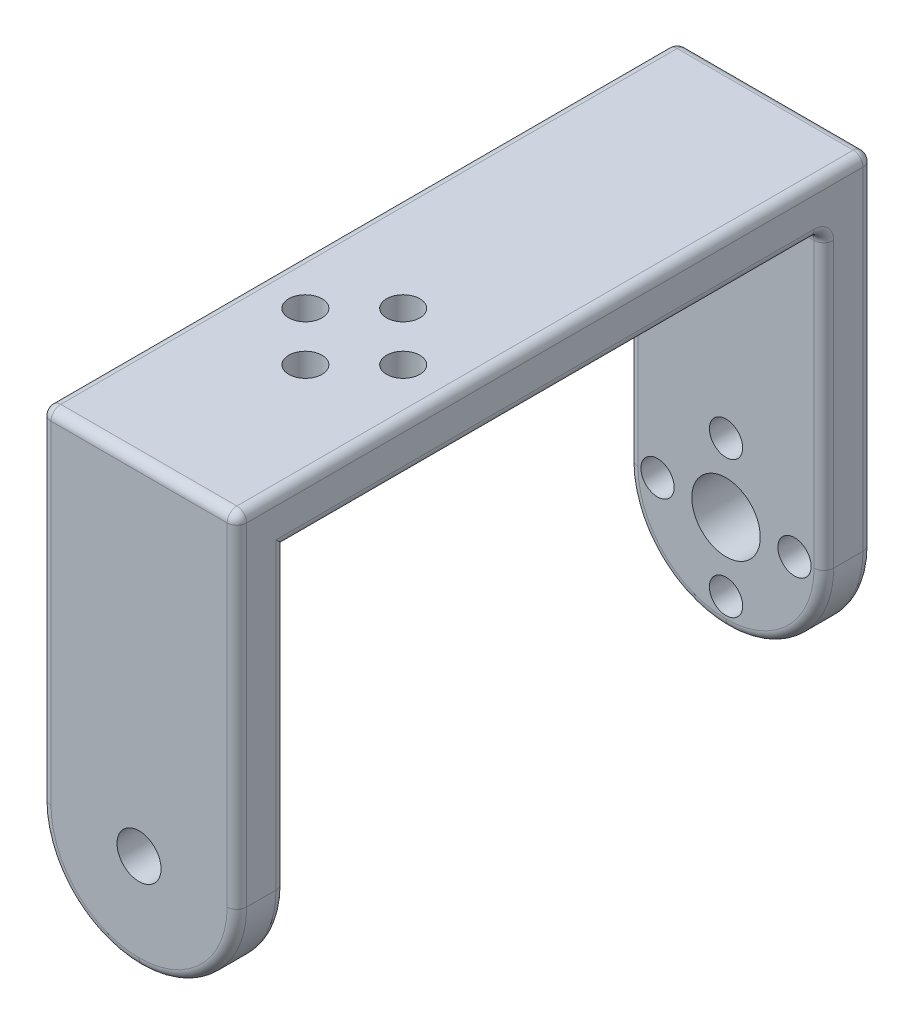
SolidWorks part; units mm, degrees
ref_plane "前视基准面" through (0, 0, 0) normal (0, 0, 1) x (1, 0, 0)
ref_plane "上视基准面" through (0, 0, 0) normal (0, 1, 0) x (1, 0, 0)
ref_plane "右视基准面" through (0, 0, 0) normal (1, 0, 0) x (0, 0, -1)
other "Configuration Table"
sketch "草图1" plane through (0, 0, 0) normal (1, 0, 0) x (0, 0, -1)
  line L0 (0, 0) -> (0, 40)
  line L1 (0, 40) -> (55, 40)
  line L2 (55, 40) -> (55, 0)
  line L3 (55, 0) -> (60, 0)
  line L4 (60, 0) -> (60, 45)
  line L5 (60, 45) -> (-5, 45)
  line L6 (-5, 45) -> (-5, 0)
  line L7 (-5, 0) -> (0, 0)
  dimension "D1" = 5
  dimension "D2" = 5
  dimension "D3" = 5
  dimension "D4" = 55
  dimension "D5" = 40
extrude "凸台-拉伸1" add sketch "草图1" along normal blind 20
fillet "圆角1" radius 10 4 edges at (0, 0, -57.5) (20, 0, -57.5) (0, 0, 2.5) (20, 0, 2.5)
hole_wizard "M3 间隙孔1" positions "草图2" profile "草图3" hole size "M3" standard "GB"
sketch "草图2" plane through (0, 0, -55) normal (0, 0, 1) x (1, 0, 0)
  circle A0 centre (10, 10) radius 7
  point P5 (10, 17)
  point P7 (3, 10)
  point P9 (17, 10)
  point P11 (10, 3)
  dimension "D1" = 14
sketch "草图3" plane through (10, 3, -55) normal (1, 0, 0) x (0, -1, 0)
  line L0 (0, 0) -> (0, 21.0215)
  line L1 (0, 21.0215) -> (1.7, 20)
  line L2 (1.7, 20) -> (1.7, 0)
  line L5 (1.7, 0) -> (0, 0)
  line L10 (0, 21.0215) -> (-1.7, 20) construction
  line L11 (0, -6.35) -> (0, 107.95) construction
  dimension "孔直径" = 3.4
  dimension "孔深度" = 20
  dimension "导头角度" = 118
hole_wizard "M4 间隙孔1" positions "草图4" profile "草图5" hole size "M4" standard "GB"
sketch "草图4" plane through (0, 0, 0) normal (0, 0, -1) x (-1, 0, 0)
  point P0 (-10, 10)
sketch "草图5" plane through (10, 10, 0) normal (1, 0, 0) x (0, 1, 0)
  line L0 (0, 0) -> (0, 21.3519)
  line L1 (0, 21.3519) -> (2.25, 20)
  line L2 (2.25, 20) -> (2.25, 0)
  line L5 (2.25, 0) -> (0, 0)
  line L10 (0, 21.3519) -> (-2.25, 20) construction
  line L11 (0, -6.35) -> (0, 107.95) construction
  dimension "孔直径" = 4.5
  dimension "孔深度" = 20
  dimension "导头角度" = 118
hole_wizard "M3 间隙孔2" positions "草图6" profile "草图7" hole size "M3" standard "GB" end condition through all
sketch "草图6" plane through (0, 45, 0) normal (0, 1, 0) x (1, 0, 0)
  line L0 (20, 60) -> (20, -5) construction
  line L1 (20, -5) -> (0, -5) construction
  circle A0 centre (10, 17) radius 5
  point P8 (10, 22)
  point P10 (5, 17)
  point P12 (10, 12)
  point P14 (15, 17)
  dimension "D1" = 10
  dimension "D2" = 10
  dimension "D3" = 22
sketch "草图7" plane through (15, 45, -17) normal (1, 0, 0) x (0, 0, 1)
  line L0 (0, 0) -> (0, 45)
  line L1 (0, 45) -> (1.7, 45)
  line L2 (1.7, 45) -> (1.7, 0)
  line L5 (1.7, 0) -> (0, 0)
  line L11 (0, -6.35) -> (0, 107.95) construction
  dimension "通孔孔直径" = 3.4
  dimension "通孔孔深度" = 45
fillet "圆角2" radius 1 23 edges at (0, 40, -27.5) (20, 40, -27.5) (0, 27.5, 5) (20, 27.5, 5) (17.0711, 2.9289, 5) (20, 25, 0) (17.0711, 2.9289, 0) (2.9289, 2.9289, 0) (0, 25, -55) (20, 25, -55) (17.0711, 2.9289, -55) (20, 27.5, -60) (17.0711, 2.9289, -60) (2.9289, 2.9289, -60) (20, 45, -27.5) (0, 45, -27.5) (10, 45, 5) (2.9289, 2.9289, 5) (0, 25, 0) (2.9289, 2.9289, -55) (10, 40, -55) (10, 45, -60) (0, 27.5, -60)
sketch "草图8" plane through (0, 0, -60) normal (0, 0, -1) x (-1, 0, 0)
  circle A0 centre (-10, 10) radius 3.5
  dimension "D1" = 7
extrude "切除-拉伸1" cut sketch "草图8" against normal blind 10
